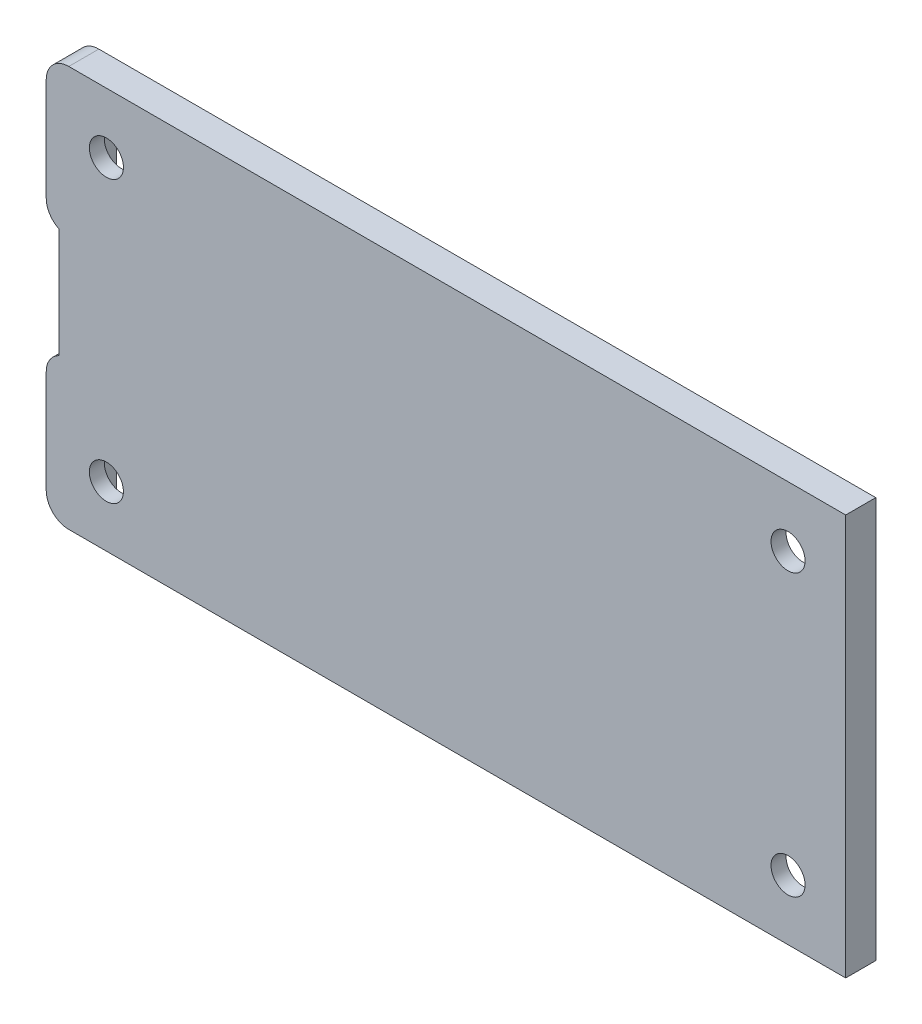
SolidWorks part; units mm, degrees
ref_plane "Front Plane" through (0, 0, 0) normal (0, 0, 1) x (1, 0, 0)
ref_plane "Top Plane" through (0, 0, 0) normal (0, 1, 0) x (1, 0, 0)
ref_plane "Right Plane" through (0, 0, 0) normal (1, 0, 0) x (0, 0, -1)
sketch "Sketch1" plane through (0, 0, 0) normal (0, 0, 1) x (1, 0, 0)
  line L1 (0, 0) -> (79.75, 0)
  line L2 (0, 0) -> (0, 40)
  line L3 (0, 40) -> (79.75, 40)
  line L4 (79.75, 0) -> (79.75, 40)
  dimension "D1" = 40
  dimension "D2" = 79.75
extrude "Boss-Extrude1" add sketch "Sketch1" along normal blind 3
sketch "Sketch2" plane through (0, 0, 3) normal (0, 0, 1) x (1, 0, 0)
  line L0 (0, 40) -> (0, 0) construction
  line L1 (0, 25.25) -> (2.25, 25.25)
  line L2 (0, 25.25) -> (0, 14.75)
  line L3 (0, 14.75) -> (2.25, 14.75)
  line L4 (2.25, 25.25) -> (2.25, 14.75)
  line L5 (0, 20) -> (2.25, 20) construction
  dimension "D1" = 2.25
  dimension "D2" = 10.5
extrude "Cut-Extrude1" cut sketch "Sketch2" against normal through all
fillet "Fillet2" radius 2.25 2 edges at (0, 14.75, 1.5) (0, 25.25, 1.5)
fillet "Fillet1" radius 2.25 2 edges at (0, 0, 1.5) (0, 40, 1.5)
sketch "Sketch6" plane through (0, 0, 3) normal (0, 0, 1) x (1, 0, 0)
  line L2 (1.25, 25.4844) -> (1.25, 14.5156)
  line L4 (2.25, 25.25) -> (2.25, 14.75)
  arc A0 (0, 27.5) -> (2.25, 25.25) centre (2.25, 27.5) ccw construction
  arc A1 (2.25, 14.75) -> (0, 12.5) centre (2.25, 12.5) ccw construction
  arc A2 (1.25, 25.4844) -> (2.25, 25.25) centre (2.25, 27.5) ccw
  arc A3 (1.25, 14.5156) -> (2.25, 14.75) centre (2.25, 12.5) cw
  dimension "D1" = 1
  dimension "D2" = 2.25
  dimension "D3" = 2.25
extrude "Boss-Extrude4" add sketch "Sketch6" against normal blind 3.7
sketch "Sketch7" plane through (0, 0, 0) normal (0, 0, -1) x (-1, 0, 0)
  line L0 (-2.25, 0) -> (-79.75, 0) construction
  line L1 (-79.75, 40) -> (-2.25, 40) construction
  line L2 (0, 37.75) -> (0, 27.5) construction
  line L4 (-4, 37.75) -> (-77.5, 37.75)
  line L8 (-4, 37.75) -> (-4, 2.25)
  line L9 (-4, 2.25) -> (-77.5, 2.25)
  line L10 (-77.5, 37.75) -> (-77.5, 2.25)
  line L11 (-79.75, 0) -> (-79.75, 40) construction
  point P12 (0, 32.625)
  dimension "D1" = 2.25
  dimension "D2" = 2.25
  dimension "D3" = 2.25
  dimension "D4" = 4
extrude "oled-recess" cut sketch "Sketch7" against normal blind 1.5
sketch "Sketch9" plane through (0, 0, 3) normal (0, 0, 1) x (1, 0, 0)
  line L0 (0, 34) -> (79.75, 34) construction
  line L1 (0, 37.75) -> (0, 27.5) construction
  line L2 (79.75, 0) -> (79.75, 40) construction
  line L3 (0, 6) -> (79.75, 6) construction
  line L4 (0, 12.5) -> (0, 2.25) construction
  line L5 (6, 40) -> (6, 0) construction
  line L6 (79.75, 40) -> (2.25, 40) construction
  line L7 (2.25, 0) -> (79.75, 0) construction
  line L8 (74, 40) -> (74, 0) construction
  circle A0 centre (6, 34) radius 1.7
  circle A1 centre (74, 34) radius 1.7
  circle A2 centre (6, 6) radius 1.7
  circle A3 centre (74, 6) radius 1.7
  point P18 (0, 32.625)
  point P19 (74, 20)
  dimension "D5" = 3.4
  dimension "D6" = 3.4
  dimension "D7" = 3.4
  dimension "D8" = 3.4
  dimension "D1" = 6
  dimension "D2" = 5.75
  dimension "D3" = 14
  dimension "D4" = 14
extrude "Cut-Extrude5" cut sketch "Sketch9" against normal through all
